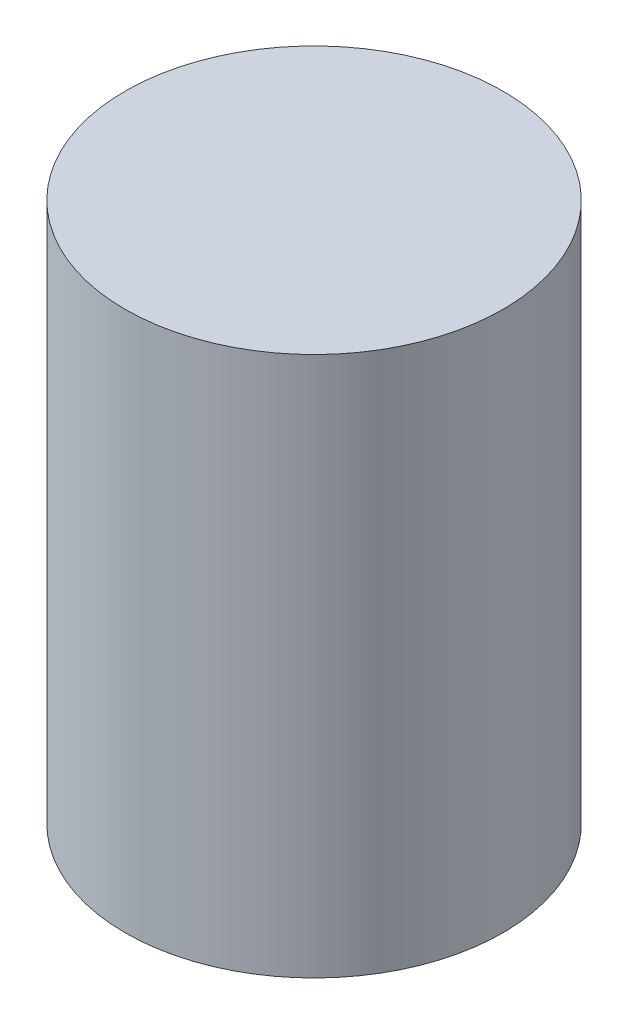
SolidWorks part; units mm, degrees
material "6061 합금"
ref_plane "정면" through (0, 0, 0) normal (0, 0, 1) x (1, 0, 0)
ref_plane "윗면" through (0, 0, 0) normal (0, 1, 0) x (1, 0, 0)
ref_plane "우측면" through (0, 0, 0) normal (1, 0, 0) x (0, 0, -1)
sketch "스케치1" plane through (0, 0, 0) normal (0, 1, 0) x (1, 0, 0)
  circle A0 centre (0, 0) radius 49
  circle A1 centre (0, 0) radius 35
  dimension "D1" = 98
  dimension "D2" = 70
extrude "보스-돌출1" add sketch "스케치1" along normal blind 140
extrude "보스-돌출2" add sketch "스케치1<2>" along normal blind 30 contours A1 region at (0, 0, 0)
sketch "스케치1<2>" plane through (0, 0, 0) normal (0, 1, 0) x (1, 0, 0) same geometry as "스케치1"
extrude "보스-돌출3" add sketch "스케치1<3>" against normal blind 30 from surface contours A1 region at (0, 0, 0) starting at face at (0, 140, 49)
sketch "스케치1<3>" plane through (0, 0, 0) normal (0, 1, 0) x (1, 0, 0) same geometry as "스케치1"
ref_plane "평면1" through (0, 118, 0) normal (0, 1, 0) x (1, 0, 0)
sketch "스케치3" plane through (0, 118, 0) normal (0, 1, 0) x (1, 0, 0)
  circle A0 centre (0, 0) radius 49
  dimension "D1" = 98
sketch "스케치4" plane through (0, 0, 0) normal (1, 0, 0) x (0, 0, -1)
  line L0 (0, 140) -> (0, 0) construction
  line L1 (49, 140) -> (-49, 140) construction
  line L2 (49, 0) -> (-49, 0) construction
